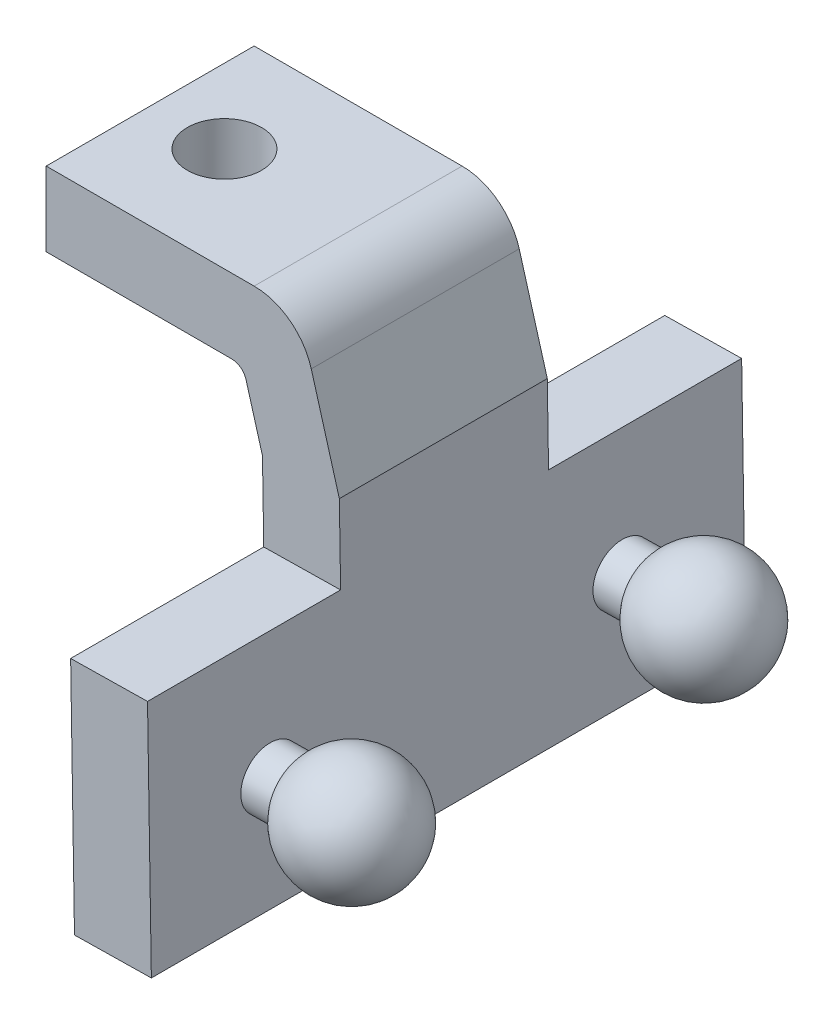
SolidWorks part; units mm, degrees
ref_plane "前视基准面" through (0, 0, 0) normal (0, 0, 1) x (1, 0, 0)
ref_plane "上视基准面" through (0, 0, 0) normal (0, 1, 0) x (1, 0, 0)
ref_plane "右视基准面" through (0, 0, 0) normal (1, 0, 0) x (0, 0, -1)
other "Configuration Table"
sketch "草图1" plane through (0, 0, 0) normal (0, 0, 1) x (1, 0, 0)
  line L0 (0, 0) -> (6.2454, 0)
  line L1 (6.7262, -0.3628) -> (7.2802, -2.304)
  line L2 (7.2802, -2.304) -> (7.4521, -12.9425)
  line L3 (7.4521, -12.9425) -> (10.04, -12.9007)
  line L4 (10.04, -12.9007) -> (9.868, -2.2622)
  line L5 (9.868, -2.2622) -> (8.9232, 1.0488)
  line L6 (0, 2.5) -> (7, 2.5)
  line L7 (0, 0) -> (0, 2.5)
  arc A0 (6.2454, 0) -> (6.7262, -0.3628) centre (6.2454, -0.5) cw
  arc A1 (8.9232, 1.0488) -> (7, 2.5) centre (7, 0.5) ccw
  dimension "D1" = 7
  dimension "D3" = 2
  dimension "D6" = 0.5
  dimension "D2" = 2.5
  dimension "D4" = 165
  dimension "D5" = 2.5
extrude "凸台-拉伸1" add sketch "草图1" along normal mid plane 7
sketch "草图2" plane through (0, 0, 0) normal (0, -1, 0) x (1, 0, 0)
  circle A0 centre (2.5, 0) radius 1.25
  dimension "D1" = 2.5
  dimension "D2" = 2.5
extrude "切除-拉伸3" cut sketch "草图2" against normal blind 5.5
sketch "草图3" plane through (9.8289, 0.1589, 0) normal (0.9999, 0.0162, 0) x (0, 0, -1)
  line L0 (-3.5, -13.0613) -> (3.5, -13.0613) construction
  line L1 (-10, -5.0613) -> (10, -5.0613)
  line L2 (-10, -5.0613) -> (-10, -13.0613)
  line L3 (-10, -13.0613) -> (10, -13.0613)
  line L4 (10, -5.0613) -> (10, -13.0613)
  line L5 (-10, -5.0613) -> (10, -13.0613) construction
  line L6 (-10, -13.0613) -> (10, -5.0613) construction
  point P0 (0, -9.0613)
  dimension "D1" = 20
  dimension "D2" = 8
extrude "凸台-拉伸2" add sketch "草图3" against normal up to vertex (2.5882 mm away) up to point (7.2802, -2.304, -3.5)
sketch "草图4" plane through (9.8289, 0.1589, 0) normal (0.9999, 0.0162, 0) x (0, 0, -1)
  circle A0 centre (-5.9281, -9.2792) radius 1
  dimension "D1" = 2
extrude "凸台-拉伸3" add sketch "草图4" along normal blind 1
ref_axis "基准轴1" through (11.011, -9.1024, 5.9281) along (-0.9999, -0.0162, 0)
ref_plane "基准面1" through (0.15, -9.278, 0) normal (-0.0162, 0.9999, 0) x (-0.9999, -0.0162, 0)
sketch "草图5" plane through (0.15, -9.278, 0) normal (-0.0162, 0.9999, 0) x (-0.9999, -0.0162, 0)
  line L0 (-10.8302, 5.9281) -> (-14.5622, 5.9281)
  line L1 (-10.8302, 6.9281) -> (-10.8302, 4.9281) construction
  line L2 (-10.8302, 5.9281) -> (-10.8302, 6.9281)
  arc A0 (-10.8302, 6.9281) -> (-14.5622, 5.9281) centre (-12.5622, 5.9281) ccw
  dimension "D1" = 4
revolve "旋转1" add sketch "草图5" angle 360 about L0
mirror "镜向1" about plane through (0, 0, 0) normal (0, 0, 1) of "凸台-拉伸3", "旋转1"
